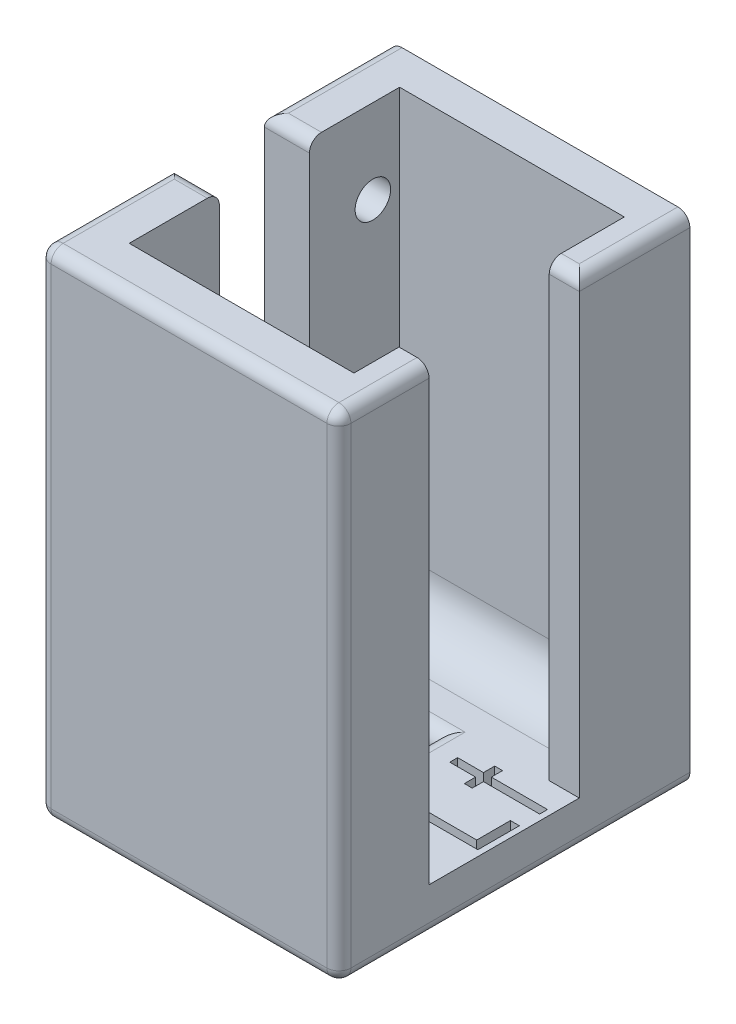
SolidWorks part; units mm, degrees
ref_plane "Front Plane" through (0, 0, 0) normal (0, 0, 1) x (1, 0, 0)
ref_plane "Top Plane" through (0, 0, 0) normal (0, 1, 0) x (1, 0, 0)
ref_plane "Right Plane" through (0, 0, 0) normal (1, 0, 0) x (0, 0, -1)
sketch "Sketch2" plane through (0, 0, 0) normal (0, 1, 0) x (1, 0, 0)
  line L0 (-9.5, -11.43) -> (9.5, -11.43)
  line L5 (12.04, -14.43) -> (-13.31, -14.43)
  line L10 (-13.31, -14.43) -> (-13.31, 15.24)
  line L15 (-13.31, 15.24) -> (12.04, 15.24)
  line L16 (12.04, 15.24) -> (12.04, 7.62)
  line L17 (12.04, -14.43) -> (12.04, -5.08)
  line L18 (12.04, 7.62) -> (9.5, 7.62)
  line L19 (9.5, 7.62) -> (9.5, 11.43)
  line L20 (9.5, 11.43) -> (-9.5, 11.43)
  line L21 (-9.5, 11.43) -> (-9.5, -11.43)
  line L22 (12.04, -5.08) -> (9.5, -5.08)
  line L24 (9.5, -11.43) -> (9.5, -5.08)
  point P6 (0, 11.43)
  point P12 (-9.5, 0)
  dimension "D1" = 22.86
  dimension "D2" = 19
  dimension "D3" = 3.81
  dimension "D4" = 3.81
  dimension "D5" = 7.62
  dimension "D6" = 2.54
  dimension "D7" = 5.08
  dimension "D8" = 3
extrude "Boss-Extrude2" add sketch "Sketch2" along normal blind 38.1
sketch "Sketch1" plane through (0, 0, 0) normal (0, 1, 0) x (1, 0, 0)
  line L1 (-13.31, -14.43) -> (12.04, -14.43)
  line L2 (-13.31, -14.43) -> (-13.31, 15.24)
  line L3 (-13.31, 15.24) -> (12.04, 15.24)
  line L4 (12.04, -14.43) -> (12.04, 15.24)
  point P0 (0, 0)
extrude "Boss-Extrude3" add sketch "Sketch1" against normal blind 3.81
sketch "Sketch3" plane through (0, 0, 0) normal (0, 1, 0) x (1, 0, 0)
  line L1 (-1.88, -3.81) -> (1.12, -3.81)
  line L2 (-1.88, -3.81) -> (-1.88, 3.81)
  line L3 (-1.88, 3.81) -> (1.12, 3.81)
  line L4 (1.12, -3.81) -> (1.12, 3.81)
  line L5 (-9.5, -11.43) -> (-9.5, 11.43) construction
  point P6 (-1.88, 0)
  dimension "D1" = 7.62
  dimension "D2" = 3
  dimension "D3" = 7.62
extrude "Cut-Extrude1" cut sketch "Sketch3" against normal through all
sketch "Sketch4" plane through (-9.5, 0, 0) normal (1, 0, 0) x (0, 0, -1)
  line L0 (-11.43, 38.1) -> (11.43, 38.1) construction
  line L1 (-3.81, 38.1) -> (3.81, 38.1)
  line L2 (-3.81, 38.1) -> (-3.81, 8)
  line L3 (-3.81, 8) -> (3.81, 8)
  line L4 (3.81, 38.1) -> (3.81, 8)
  line L5 (-11.43, 0) -> (11.43, 0) construction
  line L6 (-11.43, 38.1) -> (11.43, 38.1) construction
  point P10 (0, 38.1)
  point P11 (0, 38.1)
  dimension "D1" = 8
  dimension "D2" = 7.62
extrude "Cut-Extrude2" cut sketch "Sketch4" against normal through all
sketch "Sketch5" plane through (-9.5, 0, 0) normal (1, 0, 0) x (0, 0, -1)
  line L1 (-11.43, 0) -> (11.43, 0) construction
  circle A0 centre (-9.17, 31) radius 1.5
  circle A1 centre (8.23, 31) radius 1.5
  dimension "D3" = 3
  dimension "D1" = 2.26
  dimension "D2" = 17.4
  dimension "D4" = 31
extrude "Cut-Extrude3" cut sketch "Sketch5" against normal through all
sketch "Sketch6" plane through (0, 0, 14.43) normal (0, 0, 1) x (1, 0, 0)
  line L0 (-13.31, 38.1) -> (-13.31, -3.81) construction
  line L3 (-1.88, -3.81) -> (-1.88, 0) construction
  line L8 (12.04, 38.1) -> (12.04, 0) construction
  line L11 (-13.31, 38.1) -> (-9.5, 38.1) construction
  circle A0 centre (-11.405, 19.05) radius 1.45
  circle A1 centre (-3.81, -1.905) radius 1.45
  point P9 (-1.88, -1.905)
  point P20 (-11.405, 38.1)
  point P26 (12.04, 19.05)
  dimension "D1" = 2.9
  dimension "D2" = 9.5
extrude "Cut-Extrude4" cut sketch "Sketch6" against normal offset from surface (24.844 mm away) 6.604 up to face at (-11.405, 23.05, -3.81) offset beyond the face yes
fillet "Fillet1" radius 4 2 edges at (0, 0, -11.43) (0, 0, 11.43)
mirror "Mirror1" about plane through (0, 0, 0) normal (0, 0, 1) of bodies 106 120
delete or keep bodies "Body-Delete/Keep 1" type keep bodies bodies 116
fillet "Fillet4" radius 2.54 2 edges at (-11.405, 8, -3.81) (-11.405, 8, 3.81)
fillet "Fillet2" radius 1.016 11 edges at (-0.635, -3.81, 15.24) (-13.31, 17.145, 15.24) (-0.635, 38.1, 15.24) (12.04, 17.145, 15.24) (-13.31, -3.81, 0.405) (12.04, -3.81, 0.405) (12.04, 38.1, 11.43) (-13.31, 38.1, 9.525) (-13.31, 38.1, -9.12) (-11.405, 38.1, -3.81) (-11.405, 38.1, 3.81)
fillet "Fillet3" radius 1.27 4 edges at (-0.38, 0, -3.81) (-1.88, 0, 0) (-0.38, 0, 3.81) (1.12, 0, 0)
fillet "Fillet5" radius 1.016 2 edges at (10.77, 38.1, -5.08) (12.04, 38.1, -9.755)
ref_plane "Plane1" through (-15.85, 0, 0) normal (-1, 0, 0) x (0, 0, 1)
sketch "Sketch7" plane through (0, 0, 0) normal (0, 1, 0) x (1, 0, 0)
  line L0 (11.5383, -3.9427) -> (11.5383, 17.9144) construction
  text T0 "Lt\r\n" font "Century Gothic" height in points 28
extrude "Cut-Extrude5" cut sketch "Sketch7" against normal blind 1.27
equation "\".30.83in\"=0.83"
